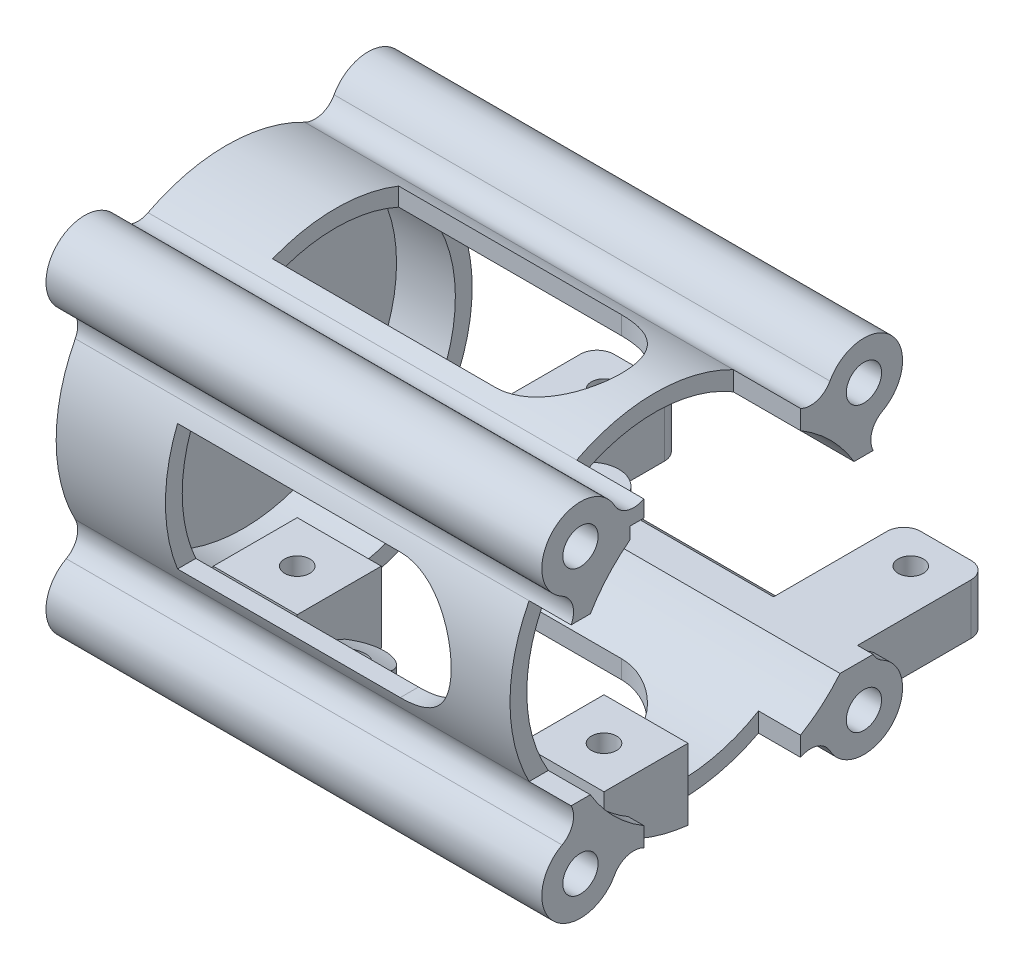
SolidWorks part; units mm, degrees
material "ABS"
ref_plane "Спереди" through (0, 0, 0) normal (0, 0, 1) x (1, 0, 0)
ref_plane "Сверху" through (0, 0, 0) normal (0, 1, 0) x (1, 0, 0)
ref_plane "Справа" through (0, 0, 0) normal (1, 0, 0) x (0, 0, -1)
sketch "Эскиз1" plane through (0, 0, 0) normal (1, 0, 0) x (0, 0, -1)
  circle A0 centre (0, 0) radius 20.25
  dimension "D1" = 40.5
extrude "Бобышка-Вытянуть1" add sketch "Эскиз1" along normal blind 2
sketch "Эскиз2" plane through (0, 0, 0) normal (-1, 0, 0) x (0, 0, 1)
  circle A0 centre (0, 0) radius 3.5
  dimension "D1" = 7
extrude "Вырез-Вытянуть1" cut sketch "Эскиз2" against normal through all
sketch "Эскиз3" plane through (2, 0, 0) normal (1, 0, 0) x (0, 0, -1)
  circle A0 centre (0, 0) radius 10.25
  circle A1 centre (0, 0) radius 20.25
  circle A2 centre (0, 0) radius 20.25 construction
  dimension "D1" = 20.5
extrude "Бобышка-Вытянуть2" add sketch "Эскиз3" along normal blind 4.1
sketch "Эскиз5" plane through (6.1, 0, 0) normal (1, 0, 0) x (0, 0, -1)
  circle A0 centre (0, 0) radius 16.25
  circle A1 centre (0, 0) radius 20.25
  circle A2 centre (0, 0) radius 20.25 construction
  dimension "D2" = 32.5
extrude "Бобышка-Вытянуть3" add sketch "Эскиз5" along normal blind 5.4
sketch "Эскиз6" plane through (11.5, 0, 0) normal (1, 0, 0) x (0, 0, -1)
  circle A0 centre (0, 0) radius 18.25
  circle A1 centre (0, 0) radius 20.25
  circle A2 centre (0, 0) radius 20.25 construction
  dimension "D2" = 36.5
extrude "Бобышка-Вытянуть4" add sketch "Эскиз6" along normal blind 47.5
sketch "Эскиз7" plane through (0, 0, 0) normal (-1, 0, 0) x (0, 0, 1)
  line L0 (0, 0) -> (-14.3189, -14.3189) construction
  line L1 (-14.3189, -14.3189) -> (14.3189, 14.3189) construction
  line L2 (0, 0) -> (-14.3189, 14.3189) construction
  line L3 (-14.3189, 14.3189) -> (14.3189, -14.3189) construction
  circle A0 centre (0, 0) radius 20.25 construction
  circle A1 centre (-9.1924, 9.1924) radius 1.5
  dimension "D1" = 13
  dimension "D2" = 3
extrude "Вырез-Вытянуть2" cut sketch "Эскиз7" against normal through all
pattern_circular "Круговой массив1" count 4 over 360 about axis through (0, 0, 0) along (1, 0, 0) of "Вырез-Вытянуть2"
fillet "Скругление1" radius 0.5 5 edges at (6.1, 0, -10.25) (11.5, 0, -16.25) (6.1, 0, -16.25) (11.5, 0, -18.25) (2, 0, -10.25)
sketch "Эскиз9" plane through (0, 0, 0) normal (-1, 0, 0) x (0, 0, 1)
  line L0 (-21.4838, 21.4838) -> (21.4838, -21.4838) construction
  line L1 (21.4838, 21.4838) -> (-21.4838, -21.4838) construction
  line L2 (0, 0) -> (0, 20.25) construction
  circle A0 centre (0, 0) radius 20.25 construction
  circle A1 centre (-16.8645, 16.8645) radius 2.1
  circle A2 centre (-16.8645, 16.8645) radius 4.6
  point P4 (0, 0)
  point P6 (0, 0)
  point P27 (0, 0)
  dimension "D3" = 4.2
  dimension "D4" = 9.2
  dimension "D1" = 45
  dimension "D2" = 45
  dimension "D5" = 23.85
extrude "Бобышка-Вытянуть6" add sketch "Эскиз9" against normal up to surface (59 mm away) up to face at (59, 0, -20.25)
sketch "Эскиз10" plane through (0, 0, 0) normal (-1, 0, 0) x (0, 0, 1)
  line L0 (-16.8645, 16.8645) -> (-9.1924, 9.1924) construction
  arc A0 (-12.8187, 19.0535) -> (-9.32, 17.9778) centre (-10.5219, 20.2961) ccw
  arc A1 (-9.32, 17.9778) -> (-12.3355, 16.0592) centre (0, 0) ccw
  arc A2 (-16.0592, 12.3355) -> (-12.3355, 16.0592) centre (0, 0) ccw construction
  arc A3 (-19.0535, 12.8187) -> (-12.8187, 19.0535) centre (-16.8645, 16.8645) ccw
  arc A4 (-12.3355, 16.0592) -> (-16.0592, 12.3355) centre (-16.8645, 16.8645) ccw construction
  arc A5 (-19.0535, 12.8187) -> (-17.9778, 9.32) centre (-20.2961, 10.5219) cw
  arc A6 (-16.0592, 12.3355) -> (-17.9778, 9.32) centre (0, 0) ccw
  arc M15 (-16.0592, 12.3355) -> (-12.3355, 16.0592) centre (0, 0) ccw
  arc M16 (-12.3355, 16.0592) -> (-16.0592, 12.3355) centre (-16.8645, 16.8645) ccw
extrude "Бобышка-Вытянуть7" add sketch "Эскиз10" against normal up to surface (59 mm away) contours A0 M16 M15 | A5 M16 M15
pattern_circular "Круговой массив3" count 4 over 360 about axis through (0, 0, 0) along (1, 0, 0) of "Бобышка-Вытянуть7", "Бобышка-Вытянуть6"
sketch "Эскиз11" plane through (0, 0, 0) normal (0, 1, 0) x (1, 0, 0)
  line L0 (59, -9.32) -> (59, 9.32) construction
  line L1 (13, 7.5) -> (39.5, 7.5)
  line L2 (13, 7.5) -> (13, -7.5)
  line L3 (13, -7.5) -> (39.5, -7.5)
  line L5 (0, 9.32) -> (0, -9.32) construction
  arc A0 (39.5, -7.5) -> (39.5, 7.5) centre (39.5, 0) ccw
  point P1 (47, 0)
  point P7 (59, 0)
  dimension "D1" = 12
  dimension "D2" = 15
  dimension "D3" = 13
extrude "Вырез-Вытянуть3" cut sketch "Эскиз11" against normal through all and the other way through all
pattern_circular "Круговой массив4" count 2 every 270 about axis through (2, 0, 0) along (-1, 0, 0) of "Вырез-Вытянуть3"
sketch "Эскиз22" plane through (2, 0, 0) normal (1, 0, 0) x (0, 0, -1)
  circle A0 centre (0, 0) radius 18.25
  dimension "D1" = 36.5
extrude "Вырез-Вытянуть9" cut sketch "Эскиз22" along normal blind 20
ref_plane "Плоскость1" through (0, -21.4645, 0) normal (0, -1, 0) x (-1, 0, 0)
sketch "Эскиз23" plane through (0, -21.4645, 0) normal (0, -1, 0) x (-1, 0, 0)
  line L0 (-59, 9.32) -> (-59, -9.32) construction
  line L1 (-59, 9.32) -> (-54, 9.32)
  line L2 (-59, 9.32) -> (-59, -9.32)
  line L3 (-59, -9.32) -> (-54, -9.32)
  line L4 (-54, 9.32) -> (-54, -9.32)
  line L5 (-59, -9.32) -> (0, -9.32) construction
  line L6 (-59, 9.32) -> (0, 9.32) construction
  dimension "D1" = 5
extrude "Вырез-Вытянуть10" cut sketch "Эскиз23" against normal through all
pattern_circular "Круговой массив5" count 2 every 270 about axis through (2, 0, 0) along (-1, 0, 0) of "Вырез-Вытянуть10"
sketch "Эскиз25" plane through (0, 0, 0) normal (-1, 0, 0) x (0, 0, 1)
  line L1 (-0.3576, -15.7612) -> (0.6168, -15.7612)
  line L2 (-0.3576, -15.7612) -> (-0.3576, -17.0516)
  line L3 (-0.3576, -17.0516) -> (0.6168, -17.0516)
  line L4 (0.6168, -15.7612) -> (0.6168, -17.0516)
extrude "Бобышка-Вытянуть8" [suppressed] add sketch "Эскиз25" along normal blind 12
sketch "Эскиз26" plane through (0, -21.4645, 0) normal (0, -1, 0) x (-1, 0, 0)
  line L0 (0, -21.4645) -> (0, -12.8187) construction
  line L1 (-59, -21.4645) -> (0, -21.4645) construction
  circle A0 centre (-23.65, -8.3545) radius 3.5
  circle A3 centre (-23.65, -8.3545) radius 1.35
  dimension "D1" = 2.7
  dimension "D2" = 7
  dimension "D3" = 23.65
  dimension "D4" = 13.11
extrude "Бобышка-Вытянуть10" add sketch "Эскиз26" against normal up to surface (3.872 mm away)
sketch "Эскиз27" plane through (0, -21.4645, 0) normal (0, -1, 0) x (-1, 0, 0)
  line L0 (0, 12.8187) -> (0, 21.4645) construction
  line L1 (0, 21.4645) -> (-59, 21.4645) construction
  circle A0 centre (-23.65, 19.5445) radius 3.5
  circle A1 centre (-23.65, 19.5445) radius 1.35
  dimension "D1" = 23.65
  dimension "D2" = 1.92
extrude "Бобышка-Вытянуть11" add sketch "Эскиз27" against normal up to vertex (8.6458 mm away)
sketch "Эскиз28" plane through (0, -21.4645, 0) normal (0, -1, 0) x (1, 0, 0)
  circle A0 centre (23.65, 8.3545) radius 1.35
  circle A1 centre (23.65, -19.5445) radius 1.35
extrude "Вырез-Вытянуть12" cut sketch "Эскиз28" against normal up to surface (8.6458 mm away) up to face at (23.65, -12.8187, -20.8945)
sketch "Эскиз30" plane through (59, 0, 0) normal (1, 0, 0) x (0, 0, -1)
  circle A0 centre (16.8645, -16.8645) radius 2.1
  dimension "D1" = 4.2
sketch "Эскиз32" plane through (59, 0, 0) normal (1, 0, 0) x (0, 0, -1)
  line L0 (15.6908, 9.32) -> (17.9778, 9.32) construction
  line L1 (25, 9.32) -> (10, 9.32)
  line L2 (25, 9.32) -> (25, -11.68)
  line L3 (25, -11.68) -> (10, -11.68)
  line L4 (10, 9.32) -> (10, -11.68)
  line L6 (-6, 11) -> (-11, 11)
  line L7 (-6, 11) -> (-6, 16)
  line L8 (-6, 16) -> (-11, 16)
  line L9 (-11, 11) -> (-11, 16)
  dimension "D1" = 10
  dimension "D2" = 15
  dimension "D3" = 21
  dimension "D4" = 11
  dimension "D5" = 5
  dimension "D6" = 5
  dimension "D7" = 6
extrude "Вырез-Вытянуть14" cut sketch "Эскиз32" against normal blind 50
ref_plane "Плоскость2" through (0, 0, -21.4645) normal (0, 0, -1) x (-1, 0, 0)
sketch "Эскиз33" plane through (0, 0, -21.4645) normal (0, 0, -1) x (-1, 0, 0)
  line L0 (-59, -21.4645) -> (0, -21.4645) construction
  line L1 (-57.15, -11.68) -> (-47.15, -11.68)
  line L2 (-57.15, -11.68) -> (-57.15, -17.7145)
  line L3 (-57.15, -17.7145) -> (-47.15, -17.7145)
  line L4 (-47.15, -11.68) -> (-47.15, -17.7145)
  line L5 (-20.65, -11.68) -> (-10.65, -11.68)
  line L6 (-20.65, -11.68) -> (-20.65, -17.7145)
  line L7 (-20.65, -17.7145) -> (-10.65, -17.7145)
  line L8 (-10.65, -11.68) -> (-10.65, -17.7145)
  line L9 (-59, -12.8187) -> (-59, -21.4645) construction
  line L10 (-9, -11.68) -> (-59, -11.68) construction
  dimension "D1" = 10
  dimension "D2" = 6.0345
  dimension "D3" = 3.75
  dimension "D4" = 1.85
  dimension "D5" = 26.5
extrude "Бобышка-Вытянуть12" add sketch "Эскиз33" along normal blind 12 and the other way up to body
sketch "Эскиз34" plane through (0, -17.7145, 0) normal (0, -1, 0) x (1, 0, 0)
  line L0 (57.15, -33.4645) -> (47.15, -33.4645) construction
  line L1 (20.65, -33.4645) -> (10.65, -33.4645) construction
  circle A0 centre (52.15, -29.2845) radius 1.5
  circle A1 centre (15.65, -29.2845) radius 1.5
  point P10 (15.65, -33.4645)
  point P12 (52.15, -33.4645)
  dimension "D2" = 3
  dimension "D1" = 4.18
extrude "Вырез-Вытянуть15" cut sketch "Эскиз34" against normal up to next (8.3945 mm away)
sketch "Эскиз35" plane through (0, -11.68, 0) normal (0, 1, 0) x (1, 0, 0)
  line L0 (10.65, 33.4645) -> (10.65, 17.9556) construction
  line L1 (10.65, -2.2155) -> (20.65, -2.2155)
  line L2 (10.65, -2.2155) -> (10.65, -12.2155)
  line L3 (10.65, -12.2155) -> (20.65, -12.2155)
  line L4 (20.65, -2.2155) -> (20.65, -12.2155)
  line L5 (47.15, -2.2155) -> (57.15, -2.2155)
  line L6 (47.15, -2.2155) -> (47.15, -12.2155)
  line L7 (47.15, -12.2155) -> (57.15, -12.2155)
  line L8 (57.15, -2.2155) -> (57.15, -12.2155)
  line L9 (20.65, 33.4645) -> (20.65, 17.9556) construction
  line L10 (47.15, 33.4645) -> (47.15, 17.9556) construction
  line L11 (57.15, 33.4645) -> (57.15, 17.9556) construction
  line L12 (15.65, 29.2845) -> (52.15, 29.2845) construction
  line L13 (10.65, -12.2155) -> (20.65, -2.2155) construction
  line L14 (20.65, -2.2155) -> (20.5044, -2.2621) construction
  line L15 (47.15, -12.2155) -> (57.15, -2.2155) construction
  line L16 (15.65, 29.2845) -> (15.65, -7.2155) construction
  circle A0 centre (15.65, -7.2155) radius 1.5
  circle A1 centre (52.15, -7.2155) radius 1.5
  dimension "D2" = 3
  dimension "D1" = 10
extrude "Бобышка-Вытянуть14" add sketch "Эскиз35" against normal up to surface (8.4485 mm away)
sketch "Эскиз36" plane through (0, -11.68, 0) normal (0, 1, 0) x (1, 0, 0)
  circle A0 centre (15.65, -7.2155) radius 1.5
  circle A1 centre (52.15, -7.2155) radius 1.5
extrude "Вырез-Вытянуть16" cut sketch "Эскиз36" against normal through all
sketch "Эскиз37" plane through (0, -11.68, 0) normal (0, 1, 0) x (1, 0, 0)
  circle A0 centre (15.65, -7.2155) radius 2.75
  circle A1 centre (52.15, -7.2155) radius 2.75
  dimension "D1" = 5.5
extrude "Вырез-Вытянуть17" [suppressed] cut sketch "Эскиз37" along normal through all
extrude "Вырез-Вытянуть18" cut sketch "Эскиз30" against normal through all
sketch "Эскиз38" plane through (0, -21.4645, 0) normal (0, -1, 0) x (-1, 0, 0)
  line L1 (-49.1, 29.2845) -> (-50.625, 31.9259)
  line L2 (-50.625, 31.9259) -> (-53.675, 31.9259)
  line L3 (-53.675, 31.9259) -> (-55.2, 29.2845)
  line L4 (-55.2, 29.2845) -> (-53.675, 26.6431)
  line L5 (-53.675, 26.6431) -> (-50.625, 26.6431)
  line L6 (-50.625, 26.6431) -> (-49.1, 29.2845)
  line L7 (-12.6, 29.2845) -> (-14.125, 31.9259)
  line L8 (-14.125, 31.9259) -> (-17.175, 31.9259)
  line L9 (-17.175, 31.9259) -> (-18.7, 29.2845)
  line L10 (-18.7, 29.2845) -> (-17.175, 26.6431)
  line L11 (-17.175, 26.6431) -> (-14.125, 26.6431)
  line L12 (-14.125, 26.6431) -> (-12.6, 29.2845)
  line L13 (-49.1, -7.2155) -> (-50.625, -4.5741)
  line L14 (-50.625, -4.5741) -> (-53.675, -4.5741)
  line L15 (-53.675, -4.5741) -> (-55.2, -7.2155)
  line L16 (-55.2, -7.2155) -> (-53.675, -9.8569)
  line L17 (-53.675, -9.8569) -> (-50.625, -9.8569)
  line L18 (-50.625, -9.8569) -> (-49.1, -7.2155)
  line L19 (-12.6, -7.2155) -> (-14.125, -4.5741)
  line L20 (-14.125, -4.5741) -> (-17.175, -4.5741)
  line L21 (-17.175, -4.5741) -> (-18.7, -7.2155)
  line L22 (-18.7, -7.2155) -> (-17.175, -9.8569)
  line L23 (-17.175, -9.8569) -> (-14.125, -9.8569)
  line L24 (-14.125, -9.8569) -> (-12.6, -7.2155)
  circle A0 centre (-52.15, 29.2845) radius 3.05 construction
  circle A1 centre (-15.65, 29.2845) radius 3.05 construction
  circle A2 centre (-52.15, -7.2155) radius 3.05 construction
  circle A3 centre (-15.65, -7.2155) radius 3.05 construction
  dimension "D1" = 6.1
extrude "Вырез-Вытянуть19" cut sketch "Эскиз38" against normal blind 6.5
sketch "Эскиз39" plane through (54, 0, 0) normal (1, 0, 0) x (0, 0, -1)
  line L0 (9.32, 17.9778) -> (9.32, 15.6908)
  line L1 (-9.32, 17.9778) -> (-9.32, 16)
  line L2 (-9.32, 16) -> (-8.7785, 16)
  arc A0 (9.32, 17.9778) -> (-9.32, 17.9778) centre (0, 0) ccw
  arc A1 (9.32, 15.6908) -> (-8.7785, 16) centre (0, 0) ccw
  arc A2 (9.32, 17.9778) -> (-9.32, 17.9778) centre (0, 0) ccw construction
  circle A3 centre (0, 0) radius 18.25 construction
extrude "Вырез-Вытянуть20" cut sketch "Эскиз39" against normal blind 3
fillet "Скругление2" radius 2 4 edges at (10.65, -14.6972, -33.4645) (47.15, -14.6972, -33.4645) (20.65, -14.6972, -33.4645) (57.15, -14.6972, -33.4645)
